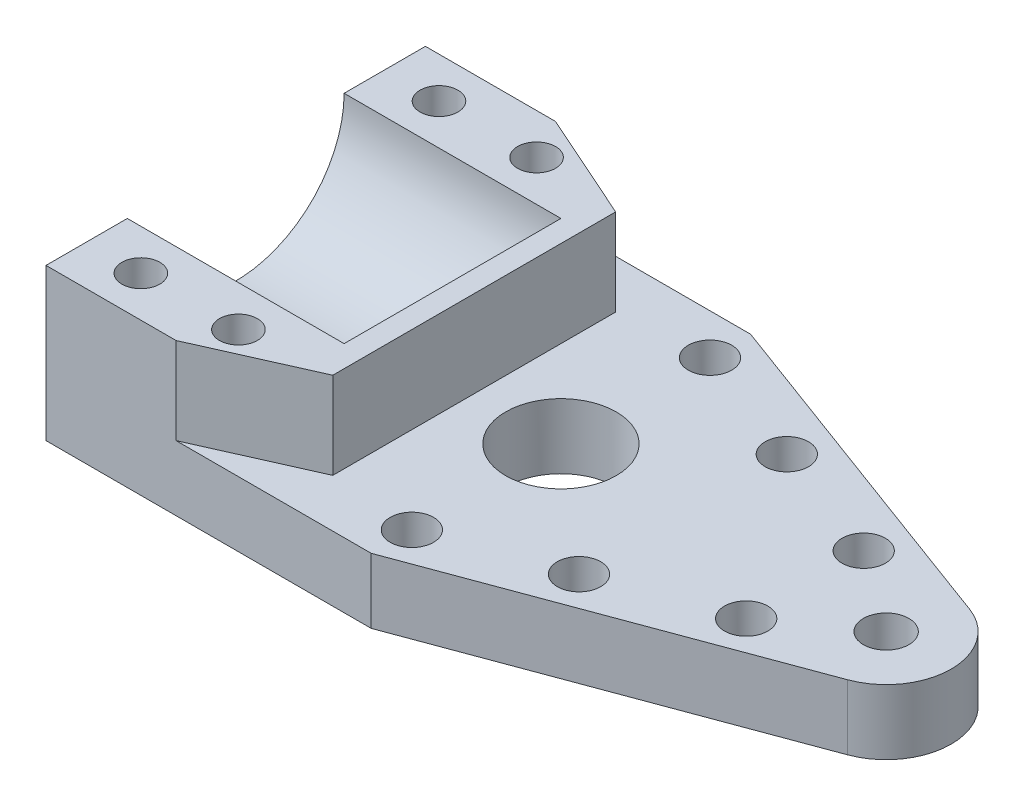
SolidWorks part; units mm, degrees
material "PEI"
ref_plane "Front Plane" through (0, 0, 0) normal (0, 0, 1) x (1, 0, 0)
ref_plane "Top Plane" through (0, 0, 0) normal (0, 1, 0) x (1, 0, 0)
ref_plane "Right Plane" through (0, 0, 0) normal (1, 0, 0) x (0, 0, -1)
sketch "Sketch1" plane through (0, 0, 0) normal (0, 1, 0) x (1, 0, 0)
  line L0 (0, 0) -> (30, 0) construction
  line L1 (-30, -17.5) -> (30, -17.5)
  line L2 (-30, -17.5) -> (-30, 17.5)
  line L3 (-30, 17.5) -> (30, 17.5)
  line L4 (30, -17.5) -> (30, 17.5)
  line L5 (-30, -17.5) -> (30, 17.5) construction
  line L6 (-30, 17.5) -> (30, -17.5) construction
  line L7 (0, 17.5) -> (0, -17.5) construction
  line L8 (0, 17.5) -> (32.0824, 5.627)
  line L9 (0, -17.5) -> (32.0824, -5.627)
  circle A0 centre (0, 0) radius 5.1
  circle A1 centre (30, 0) radius 2.1
  circle A2 centre (30, 0) radius 6
  point P0 (0, 0)
  dimension "D1" = 10.2
  dimension "D5" = 4.2
  dimension "D6" = 12
  dimension "D2" = 60
  dimension "D3" = 35
  dimension "D4" = 30
extrude "Boss-Extrude1" add sketch "Sketch1" along normal blind 14 and the other way blind 14 contours A2 L4 L9 | L4 A2 A1 | A2 L8 L4 | A2 L4 L8 L3 L2 L1 L9 A0 | L4 A2 A1 region at (-29.3054, 0, 0) region at (30.5272, 0, 6.0827) region at (27.2225, 0, 0) region at (32.7775, 0, 0) region at (30.5272, 0, -6.0827)
sketch "Sketch2" plane through (-30, 0, 0) normal (-1, 0, 0) x (0, 0, 1)
  circle A0 centre (0, 0) radius 10
  dimension "D1" = 20
extrude "Cut-Extrude1" cut sketch "Sketch2" against normal blind 20 contours A0
sketch "Sketch3" plane through (-30, 0, 0) normal (-1, 0, 0) x (0, 0, 1)
  line L0 (-28.7806, 0) -> (30.768, 0)
  line L1 (30.768, 0) -> (25.7627, 25.9835)
  line L2 (25.7627, 25.9835) -> (-26.2043, 26.646)
  line L3 (-26.2043, 26.646) -> (-28.7806, 0)
extrude "Cut-Extrude2" cut sketch "Sketch3" against normal blind 98
sketch "Sketch4" plane through (0, 0, 0) normal (0, 1, 0) x (1, 0, 0)
  line L0 (-30, 13.75) -> (0, 13.75) construction
  line L1 (-30, 17.5) -> (-30, 10) construction
  line L2 (0, 13.75) -> (0, -13.75) construction
  line L3 (0, -13.75) -> (-30, -13.75) construction
  line L4 (-30, -10) -> (-30, -17.5) construction
  line L5 (-32.6009, 0) -> (37.1544, 0) construction
  line L6 (0, 13.75) -> (37.1544, 0) construction
  line L7 (37.1544, 0) -> (0, -13.75) construction
  line L8 (0, 17.5) -> (32.0824, 5.627) construction
  line L9 (0, -17.5) -> (32.0824, -5.627) construction
  circle A0 centre (0, 13.75) radius 2
  circle A1 centre (-25, 13.75) radius 1.75
  circle A2 centre (-16, 13.75) radius 1.75
  circle A4 centre (-16, -13.75) radius 1.75
  circle A5 centre (-25, -13.75) radius 1.75
  circle A19 centre (11.2541, 9.5851) radius 2
  circle A20 centre (22.5081, 5.4203) radius 2
  circle A23 centre (22.5081, -5.4203) radius 2
  circle A24 centre (11.2541, -9.5851) radius 2
  circle A25 centre (0, -13.75) radius 2
  dimension "D4" = 3.5
  dimension "D5" = 4
  dimension "D1" = 5
  dimension "D2" = 9
  dimension "D3" = 3
extrude "Cut-Extrude3" cut sketch "Sketch4" against normal blind 98
sketch "Sketch5" plane through (0, 0, 0) normal (0, 1, 0) x (1, 0, 0)
  line L0 (-8, 24.0497) -> (-8, -23.9632)
  line L1 (-8, 24.0497) -> (56.9644, 12.8899)
  line L2 (56.9644, 12.8899) -> (49.9553, -27.9126)
  line L3 (49.9553, -27.9126) -> (-8, -23.9632)
  dimension "D1" = 8
extrude "Cut-Extrude4" cut sketch "Sketch5" against normal blind 8
chamfer "Chamfer2" distance 10 angle 24 2 edges at (-8, -4, 17.5) (-8, -4, -17.5) first distance on face at (-12.6667, -7.3333, 17.5) first distance on face at (-12.6667, -7.3333, -17.5)
sketch "Sketch6" plane through (0, -14, 0) normal (0, -1, 0) x (1, 0, 0)
  circle A0 centre (-25, 13.75) radius 3.25
  circle A1 centre (-16, 13.75) radius 3.25
  circle A2 centre (-25, -13.75) radius 3.25
  circle A3 centre (-16, -13.75) radius 3.25
  dimension "D1" = 6.5
extrude "Cut-Extrude5" cut sketch "Sketch6" against normal blind 1.5
sketch "Sketch7" plane through (0, -14, 0) normal (0, -1, 0) x (1, 0, 0)
  circle A0 centre (30, 0) radius 4.25
  dimension "D1" = 8.5
extrude "Cut-Extrude6" cut sketch "Sketch7" against normal blind 1.5
